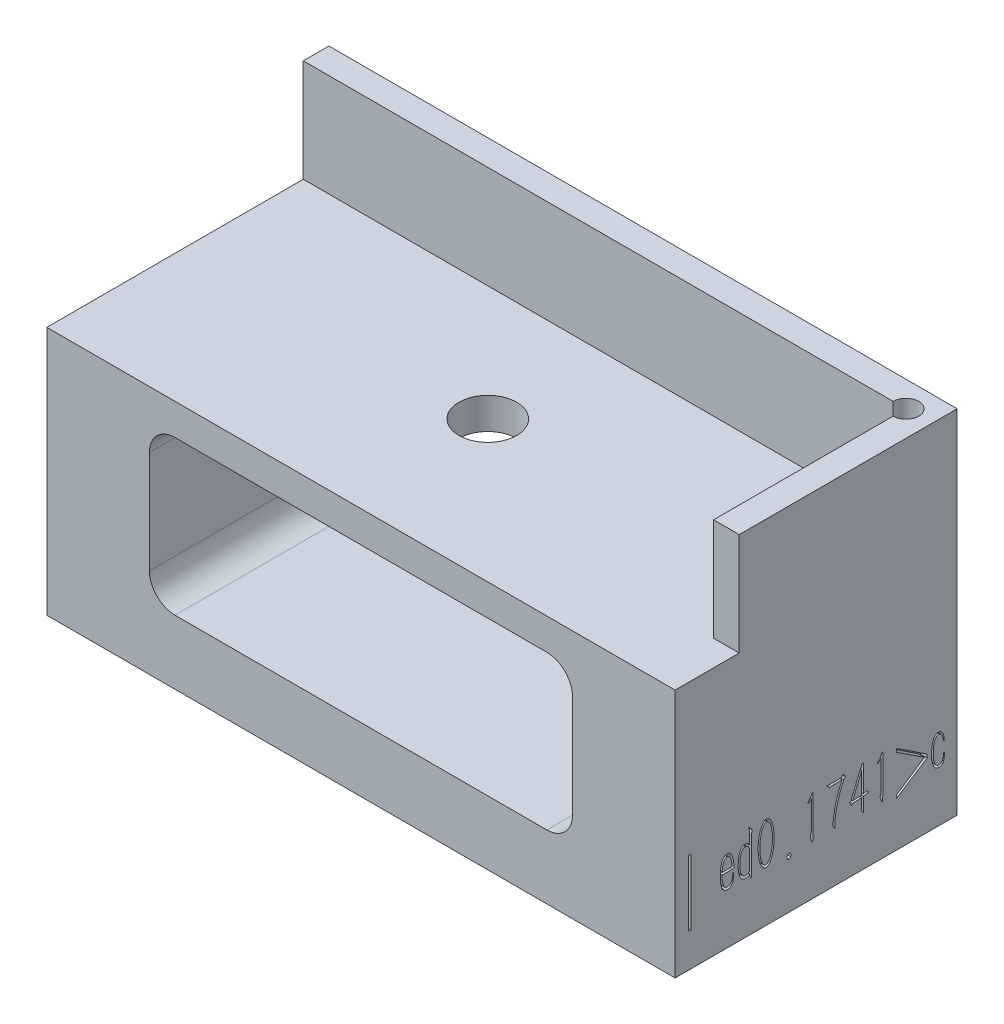
SolidWorks part; units mm, degrees
material "6061 合金"
ref_plane "前视基准面" through (0, 0, 0) normal (0, 0, 1) x (1, 0, 0)
ref_plane "上视基准面" through (0, 0, 0) normal (0, 1, 0) x (1, 0, 0)
ref_plane "右视基准面" through (0, 0, 0) normal (1, 0, 0) x (0, 0, -1)
sketch "草图1" plane through (0, 0, 0) normal (0, 1, 0) x (1, 0, 0)
  line L1 (-23.5, 9) -> (23.5, 9)
  line L2 (-23.5, 9) -> (-23.5, -9)
  line L3 (-23.5, -9) -> (23.5, -9)
  line L4 (23.5, 9) -> (23.5, -9)
  line L5 (-23.5, 9) -> (23.5, -9) construction
  line L6 (-23.5, -9) -> (23.5, 9) construction
  point P0 (0, 0)
  dimension "D1" = 47
  dimension "D2" = 18
extrude "凸台-拉伸1" add sketch "草图1" along normal blind 6
sketch "草图2" plane through (0, 6, 0) normal (0, 1, 0) x (1, 0, 0)
  line L1 (23.5, 9) -> (-23.5, 9) construction
  line L3 (23.5, 9) -> (-23.5, 9)
  line L12 (-23.5, -9) -> (23.5, -9) construction
  line L13 (-23.5, -9) -> (23.5, -9)
  line L19 (23.5, -9) -> (23.5, 9) construction
  line L20 (23.5, -9) -> (23.5, 9)
  line L21 (-23.5, -11) -> (25.5, -11)
  line L22 (25.5, -11) -> (25.5, 11)
  line L23 (25.5, 11) -> (-23.5, 11)
  line L24 (-23.5, -11) -> (-23.5, -9)
  line L25 (-23.5, 9) -> (-23.5, 11)
  dimension "D1" = 2
extrude "凸台-拉伸2" add sketch "草图2" along normal blind 8 and the other way through all
sketch "草图15" plane through (0, 0, 10) normal (0, 1, 0) x (1, 0, 0)
  line L4 (-23.5, -1) -> (25.5, -1)
  line L5 (-23.5, 21) -> (-23.5, -1)
  line L6 (25.5, 21) -> (-23.5, 21)
  line L7 (25.5, -1) -> (25.5, 21)
  line L12 (-23.5, -1) -> (25.5, -1)
  line L13 (-23.5, 21) -> (-23.5, -1)
  line L14 (25.5, 21) -> (-23.5, 21)
  line L15 (25.5, -1) -> (25.5, 21)
  dimension "D1" = 0
extrude "凸台-拉伸3" add sketch "草图15" against normal blind 5
sketch "草图12" plane through (-23.5, 0, 0) normal (-1, 0, 0) x (0, 0, 1)
  line L5 (9, 6) -> (11, 6)
  line L6 (9, 6) -> (9, 14)
  line L7 (9, 14) -> (11, 14)
  line L8 (11, 6) -> (11, 14)
extrude "切除-拉伸5" cut sketch "草图12" against normal offset from surface (37 mm away) 10 up to face at (23.5, 10, 0)
sketch "草图19" plane through (0, 0, 9) normal (0, 0, -1) x (-1, 0, 0)
  line L4 (-23.5, 6) -> (-13.5, 6)
  line L5 (-13.5, 6) -> (-13.5, 14)
  line L6 (-13.5, 14) -> (-23.5, 14)
  line L7 (-23.5, 14) -> (-23.5, 6)
  line L8 (-23.5, 6) -> (-13.5, 6)
  line L10 (-13.5, 14) -> (-23.5, 14)
  line L11 (-23.5, 14) -> (-23.5, 6)
  line L15 (-13.5, 6) -> (-13.5, 14)
  dimension "D1" = 0
extrude "凸台-拉伸4" add sketch "草图19" along normal blind 3
sketch "草图13" plane through (0, 14, 0) normal (0, 1, 0) x (1, 0, 0)
  circle A0 centre (23.5, 9) radius 1
extrude "切除-拉伸6" cut sketch "草图13" against normal up to surface (8 mm away) up to face at (4.5, 6, 2.6667)
sketch "草图5" plane through (0, -5, 0) normal (0, -1, 0) x (1, 0, 0)
  line L1 (-6.622, 9.4855) -> (18.378, 9.4855)
  line L2 (-6.622, 9.4855) -> (-6.622, -15.5145)
  line L3 (-6.622, -15.5145) -> (18.378, -15.5145)
  line L4 (18.378, 9.4855) -> (18.378, -15.5145)
  line L5 (-6.622, 9.4855) -> (18.378, -15.5145) construction
  line L6 (-6.622, -15.5145) -> (18.378, 9.4855) construction
  circle A0 centre (5.878, -3.0145) radius 2.3876 construction
  circle A1 centre (5.878, -3.0145) radius 2.3876 construction
  dimension "D1" = 25
  dimension "D2" = 25
extrude "切除-拉伸1" [suppressed] cut sketch "草图5" along normal up to surface (2.844 mm away)
sketch "草图3" plane through (0, -5, 0) normal (0, 1, 0) x (1, 0, 0)
  line L0 (-0.122, 9) -> (-0.122, 0.0145) construction
  line L1 (23.5, -6) -> (23.5, 8) construction
  line L3 (22.5, 9) -> (-23.5, 9) construction
  line L5 (-0.122, 0.0145) -> (23.5, 0.0145) construction
  circle A0 centre (-0.122, 0.0145) radius 1.3881
  circle A1 centre (-0.122, 0.0145) radius 2.5 construction
hole_wizard "打孔尺寸(%根据)内六角圆柱头螺钉的类型2" positions "3D草图1" profile "草图4" counterbore size "M4" standard "GB" end condition through all
sketch3d "3D草图1"
  point P0 (-0.122, -5, -0.0145)
sketch "草图4" plane through (-0.122, -5, -0.0145) normal (1, 0, 0) x (0, 0, -1)
  line L0 (0, 0) -> (0, 19)
  line L1 (0, 19) -> (2.25, 19)
  line L3 (2.25, 19) -> (2.25, 4.6)
  line L4 (2.25, 4.6) -> (4, 4.6)
  line L5 (4, 4.6) -> (4, 0)
  line L7 (4, 0) -> (0, 0)
  line L11 (0, -6.35) -> (0, 107.95) construction
  dimension "通孔孔直径" = 4.5
  dimension "通孔孔深度" = 19
  dimension "柱形沉头孔直径" = 8
  dimension "柱形沉头孔深度" = 4.6
sketch "草图6" [suppressed] plane through (0, -2.156, 0) normal (0, -1, 0) x (1, 0, 0)
  circle A2 centre (5.878, -3.0145) radius 5
  circle A4 centre (5.878, -3.0145) radius 2.3876 construction
hole_wizard "M4 螺纹孔4" [suppressed] positions "3D草图2" profile "草图20" tap size "M4" standard "GB"
sketch3d "3D草图2" [suppressed]
  point P0 (5.878, -2.156, -3.0145)
sketch "草图20" plane through (5.878, -2.156, -3.0145) normal (1, 0, 0) x (0, 0, -1)
  line L0 (0, 0) -> (0, 16.156)
  line L1 (0, 16.156) -> (1.65, 16.156)
  line L2 (1.65, 16.156) -> (1.65, 0)
  line L5 (1.65, 0) -> (0, 0)
  line L11 (0, -6.35) -> (0, 107.95) construction
  dimension "通孔螺纹孔钻头直径" = 3.3
  dimension "通孔螺纹孔钻头深度" = 16.156
cosmetic thread "孔螺蚊线6" [suppressed] parameters "D2"=4
sketch "草图17" [suppressed] plane through (18.378, 0, 0) normal (-1, 0, 0) x (0, 0, 1)
  line L4 (-11, -5) -> (9.4855, -5)
  line L5 (9.4855, -5) -> (9.4855, -2.156)
  line L6 (9.4855, -2.156) -> (-11, -2.156)
  line L7 (-11, -2.156) -> (-11, -5)
  line L10 (9.4855, -2.156) -> (-11, -2.156)
  line L14 (-11, -2.156) -> (-11, -5)
  line L15 (-11, -5) -> (9.4855, -5)
  line L16 (9.4855, -5) -> (9.4855, -2.156)
  dimension "D1" = 0
extrude "切除-拉伸8" [suppressed] cut sketch "草图17" against normal blind 1
sketch "草图18" [suppressed] plane through (0, -5, 0) normal (0, -1, 0) x (-1, 0, 0)
  line L0 (6.622, -9.4855) -> (6.622, 11) construction
  line L1 (-19.378, -9.4855) -> (6.622, -9.4855) construction
  circle A0 centre (6.622, -9.4855) radius 1
extrude "切除-拉伸9" [suppressed] cut sketch "草图18" against normal up to surface (2.844 mm away)
fillet "圆角1" [suppressed] radius 1
sketch "草图21" plane through (0, 0, 11) normal (0, 0, 1) x (1, 0, 0)
  text T0 "CS165MU/M"
extrude "切除-拉伸10" cut sketch "草图21" against normal blind 0.5
sketch "草图22" plane through (13.5, 0, 0) normal (-1, 0, 0) x (0, 0, 1)
  line L4 (11, 14) -> (6, 14)
  line L5 (6, 14) -> (6, 6)
  line L6 (6, 6) -> (11, 6)
  line L7 (11, 6) -> (11, 14)
  line L8 (11, 14) -> (6, 14)
  line L9 (6, 14) -> (6, 6)
  line L10 (6, 6) -> (11, 6)
  line L11 (11, 6) -> (11, 14)
  dimension "D1" = 0
extrude "切除-拉伸11" cut sketch "草图22" against normal through all
sketch "草图23" plane through (0, -5, 0) normal (0, -1, 0) x (1, 0, 0)
  line L4 (25.5, -11) -> (25.5, 11)
  line L5 (25.5, 11) -> (-23.5, 11)
  line L6 (-23.5, 11) -> (-23.5, -11)
  line L7 (-23.5, -11) -> (25.5, -11)
  line L8 (25.5, -11) -> (25.5, 11)
  line L9 (25.5, 11) -> (-23.5, 11)
  line L10 (-23.5, 11) -> (-23.5, -11)
  line L11 (-23.5, -11) -> (25.5, -11)
  dimension "D1" = 0
extrude "凸台-拉伸5" add sketch "草图23" along normal offset from surface (8.446 mm away) 3 offset beyond the face yes
sketch "草图24" plane through (0, -13.446, 0) normal (0, -1, 0) x (1, 0, 0)
  line L0 (-12.572, -3.0145) -> (12.328, -3.0145) construction
  line L1 (-12.622, 9.4855) -> (12.378, 9.4855)
  line L2 (-12.622, 9.4855) -> (-12.622, -15.5145)
  line L3 (-12.622, -15.5145) -> (12.378, -15.5145)
  line L4 (12.378, 9.4855) -> (12.378, -15.5145)
  line L5 (-12.622, 9.4855) -> (12.378, -15.5145) construction
  line L6 (-12.622, -15.5145) -> (12.378, 9.4855) construction
  point P0 (-0.122, -3.0145)
  dimension "D1" = 25
  dimension "D2" = 25
extrude "切除-拉伸12" cut sketch "草图24" against normal blind 3
sketch "草图26" plane through (0, -10.446, 0) normal (0, -1, 0) x (1, 0, 0)
  line L0 (-0.122, 9.4855) -> (-0.122, -3.0145) construction
  line L1 (12.378, 9.4855) -> (-12.622, 9.4855) construction
  line L3 (-0.122, -3.0145) -> (12.378, -3.0145) construction
  line L5 (-0.122, -9) -> (-0.122, -0.0145) construction
  circle A0 centre (-0.122, -3.0145) radius 0.8949
  dimension "D1" = 12.5
hole_wizard "M4 螺纹孔6" positions "3D草图5" profile "草图27" tap size "M4" standard "GB"
sketch3d "3D草图5"
  point P0 (-0.122, -10.446, -3.0145)
sketch "草图27" plane through (-0.122, -10.446, -3.0145) normal (1, 0, 0) x (0, 0, -1)
  line L0 (0, 0) -> (0, 5.9914)
  line L1 (0, 5.9914) -> (1.65, 5)
  line L2 (1.65, 5) -> (1.65, 0)
  line L5 (1.65, 0) -> (0, 0)
  line L10 (0, 5.9914) -> (-1.65, 5) construction
  line L11 (0, -6.35) -> (0, 107.95) construction
  dimension "螺纹孔钻头直径" = 3.3
  dimension "螺纹孔钻头深度" = 5
  dimension "导头角度" = 118
cosmetic thread "孔螺蚊线7" parameters "D1"=5, "D2"=4
sketch "草图28" plane through (0, 0, -11) normal (0, 0, -1) x (-1, 0, 0)
  line L0 (0.122, -10.446) -> (0.122, -8.446) construction
  line L1 (-0.7729, -10.446) -> (1.0169, -10.446) construction
  line L2 (0.122, -8.446) -> (15.5, -8.446) construction
  line L3 (23.5, -13.446) -> (23.5, 14) construction
  line L4 (15.5, -8.446) -> (-17.5, -8.446)
  line L5 (15.5, -8.446) -> (15.5, 3.554)
  line L6 (15.5, 3.554) -> (-17.5, 3.554)
  line L7 (-17.5, -8.446) -> (-17.5, 3.554)
  line L8 (-25.5, -13.446) -> (-25.5, 14) construction
  dimension "D1" = 2
  dimension "D2" = 12
  dimension "D3" = 8
  dimension "D4" = 8
extrude "切除-拉伸13" cut sketch "草图28" against normal through all
fillet "圆角2" radius 2 4 edges at (17.5, -8.446, 0) (-15.5, -8.446, 0) (-15.5, 3.554, 0) (17.5, 3.554, 0)
sketch "草图29" plane through (-12.5, 0, -11) normal (0, 0, 1) x (1, 0, 0)
  text T0 "CS165MU/M rail "
extrude "切除-拉伸14" cut sketch "草图29" along normal blind 0.5
sketch "草图31" plane through (12.378, 0, 0) normal (1, 0, 0) x (0, 0, -1)
  line L4 (11, -13.446) -> (11, -10.446)
  line L5 (11, -10.446) -> (-9.4855, -10.446)
  line L6 (-9.4855, -10.446) -> (-9.4855, -13.446)
  line L7 (-9.4855, -13.446) -> (11, -13.446)
  line L8 (11, -13.446) -> (11, -10.446)
  line L9 (11, -10.446) -> (-9.4855, -10.446)
  line L10 (-9.4855, -10.446) -> (-9.4855, -13.446)
  line L11 (-9.4855, -13.446) -> (11, -13.446)
  dimension "D1" = 0
extrude "切除-拉伸16" cut sketch "草图31" along normal blind 0.1741
sketch "草图30" plane through (0, -13.446, 0) normal (0, -1, 0) x (1, 0, 0)
  circle A0 centre (12.5521, 9.4855) radius 1
  circle A1 centre (-12.622, 9.4855) radius 1
extrude "切除-拉伸15" cut sketch "草图30" against normal up to surface (3 mm away) up to face at (-0.122, -10.446, -4.6645)
fillet "圆角3" [suppressed] radius 1
sketch "草图32" plane through (25.5, 0, 0) normal (1, 0, 0) x (0, 0, -1)
  text T0 "| ed0.1741>c "
extrude "切除-拉伸17" cut sketch "草图32" against normal blind 0.5
sketch "草图33" plane through (-23.5, 0, 0) normal (-1, 0, 0) x (0, 0, 1)
  text T0 "cen |"
extrude "切除-拉伸18" cut sketch "草图33" against normal blind 0.5
